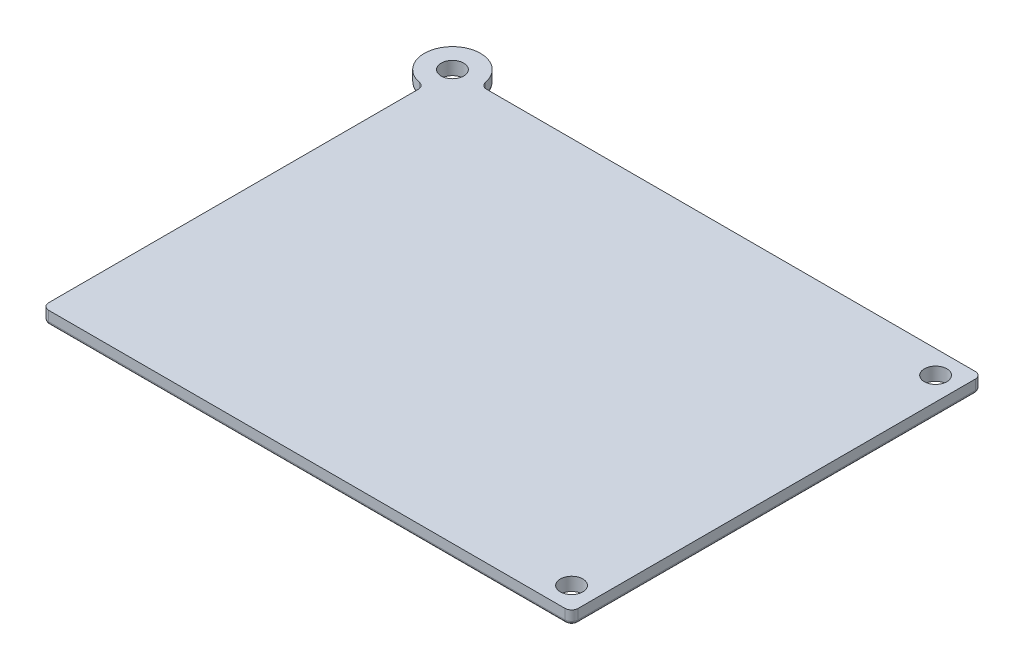
SolidWorks part; units mm, degrees
material "PVC Rigid"
ref_plane "Front Plane" through (0, 0, 0) normal (0, 0, 1) x (1, 0, 0)
ref_plane "Top Plane" through (0, 0, 0) normal (0, 1, 0) x (1, 0, 0)
ref_plane "Right Plane" through (0, 0, 0) normal (1, 0, 0) x (0, 0, -1)
sketch "Sketch1" plane through (0, 0, 0) normal (0, 1, 0) x (1, 0, 0)
  line L1 (-40, -31) -> (40, -31)
  line L2 (-40, -31) -> (-40, 25.8461)
  line L3 (-34.8461, 31) -> (40, 31)
  line L4 (40, -31) -> (40, 31)
  line L5 (-40, -31) -> (40, 31) construction
  line L6 (0, 0) -> (40, -31) construction
  arc A0 (-40, 25.8461) -> (-40.8095, 26.8278) centre (-41, 25.8461) ccw construction
  arc A1 (-35.8278, 31.8095) -> (-34.8461, 31) centre (-34.8461, 32) ccw construction
  arc A2 (-35.8278, 31.8095) -> (-40.8095, 26.8278) centre (-40, 31) ccw construction
  arc A3 (-40, 25.8461) -> (-40.8095, 26.8278) centre (-41, 25.8461) ccw
  arc A4 (-35.8278, 31.8095) -> (-34.8461, 31) centre (-34.8461, 32) ccw
  arc A5 (-35.8278, 31.8095) -> (-40.8095, 26.8278) centre (-40, 31) ccw
  point P0 (0, 0)
  dimension "D1" = 80
  dimension "D2" = 62
extrude "Main Body" add sketch "Sketch1" along normal blind 2
fillet "Corners" radius 1 3 edges at (-40, 1, 31) (40, 1, -31) (40, 1, 31)
fillet "Edge" radius 0.5 10 edges at (-39.7071, 0, 30.7071) (39.7071, 0, -30.7071) (39.7071, 0, 30.7071) (-40, 0, 2.0769) (2.0769, 0, -31) (40, 0, 0) (0, 0, 31) (-40.2285, 0, -26.4823) (-43.0052, 0, -34.0052) (-35.4823, 0, -31.2285)
sketch "Sketch7" plane through (0, 0, 0) normal (0, -1, 0) x (-1, 0, 0)
  line L0 (-39, 31) -> (34.8461, 31) construction
  line L1 (-40, -30) -> (-40, 30) construction
  line L2 (39, -31) -> (-39, -31) construction
  circle A0 centre (-36.5, 27.5) radius 1.7
  circle A1 centre (-36.5, -27.5) radius 1.7
  arc A2 (40.7143, 27.3187) -> (36.3187, 31.7143) centre (40, 31) ccw construction
  circle A4 centre (40, 31) radius 1.7
  point P9 (0, 0)
  point P14 (0, 0)
  point P15 (0, 0)
  point P16 (0, 0)
  dimension "D3" = 3.4
  dimension "D4" = 3.4
  dimension "D6" = 3.4
  dimension "D1" = 3.5
  dimension "D2" = 3.5
  dimension "D5" = 3.5
extrude "Lid Holes" cut sketch "Sketch7" against normal through all both and the other way through all
sketch "Peg Angle" plane through (0, 0, 0) normal (0, -1, 0) x (-1, 0, 0)
  line L0 (39.5, -30) -> (19.4082, -13.9542) construction
  line L1 (-39.3536, -30.3536) -> (-19.8872, -10.8872) construction
  arc A0 (-39.5, -30) -> (-39, -30.5) centre (-39, -30) ccw construction
sketch "Sketch4" plane through (0, 0, 0) normal (0, -1, 0) x (-1, 0, 0)
  line L0 (-39.3536, -30.3536) -> (-19.8872, -10.8872) construction
  line L3 (-34.4038, -19.747) -> (-28.747, -25.4038) construction
  circle A0 centre (-34.4038, -19.747) radius 2.325
  circle A1 centre (-28.747, -25.4038) radius 2.325
  point P8 (-31.5754, -22.5754)
  dimension "D1" = 4.65
  dimension "D3" = 4.65
  dimension "D2" = 4
  dimension "D4" = 8
  dimension "D5" = 11
extrude "Boss-Extrude3" add sketch "Sketch4" along normal blind 1.6
fillet "Fillet3" radius 0.05 2 edges at (34.4038, -1.6, 17.422) (28.747, -1.6, 23.0788)
pattern_linear "LPattern5" count 4 spacing 8 along (-0.7071, 0, -0.7071) of "Boss-Extrude3", "Fillet3"
sketch "Sketch9" plane through (0, 0, 0) normal (0, -1, 0) x (-1, 0, 0)
  line L0 (39.5, -30) -> (19.4082, -13.9542) construction
  line L2 (27.317, -25.3894) -> (32.3093, -19.1383) construction
  circle A0 centre (27.317, -25.3894) radius 2.325
  circle A1 centre (32.3093, -19.1383) radius 2.325
  arc A2 (39, -31) -> (40, -30) centre (39, -30) ccw construction
  point P8 (29.8131, -22.2639)
  point P11 (39.7071, -30.7071)
  dimension "D1" = 4.65
  dimension "D2" = 4.65
  dimension "D3" = 8
  dimension "D4" = 13
extrude "Pegs (Diagonal)" add sketch "Sketch9" along normal blind 1.6
fillet "Fillet6" radius 0.05 2 edges at (-27.317, -1.6, 23.0644) (-32.3093, -1.6, 16.8133)
pattern_linear "LPattern6" count 4 spacing 8 along (0.7814, 0, -0.624) of "Pegs (Diagonal)"
equation "\"D2@Sketch9\"=\"D1@Sketch9\""
equation "\"D3@Sketch4\"=\"D1@Sketch4\""
equation "\"D4@Sketch4\"=\"D2@Sketch4\"*2"
equation "\"D4@Sketch7\"=\"D3@Sketch7\""
equation "\"D5@Sketch7\"=\"D1@Sketch7\""
equation "\"D6@Sketch7\"=\"D3@Sketch7\""
